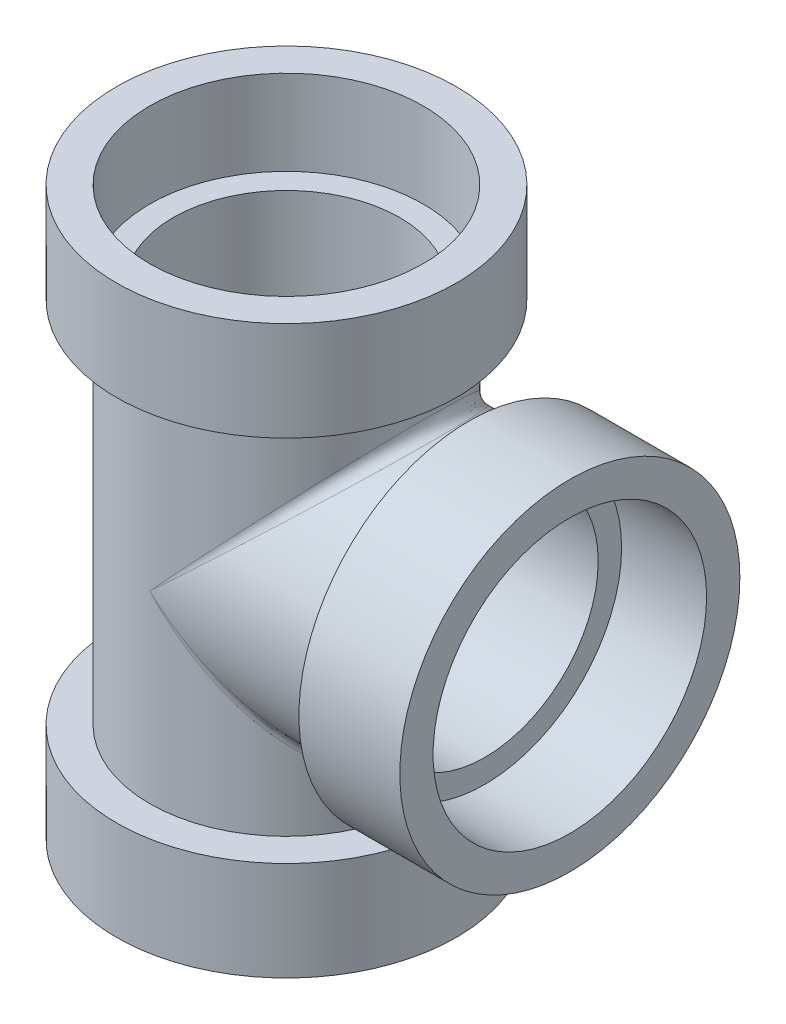
SolidWorks part; units mm, degrees
note: The reader was unsure of these and kept them because the rebuilt part matched: shared geometry of "Croquis3<2>".
ref_plane "Alzado" through (0, 0, 0) normal (0, 0, 1) x (1, 0, 0)
ref_plane "Planta" through (0, 0, 0) normal (0, 1, 0) x (1, 0, 0)
ref_plane "Vista lateral" through (0, 0, 0) normal (1, 0, 0) x (0, 0, -1)
sketch "Croquis1" plane through (0, 0, 0) normal (0, 1, 0) x (1, 0, 0)
  circle A0 centre (0, 0) radius 30
  dimension "D1" = 60
extrude "Saliente-Extruir1" add sketch "Croquis1" along normal mid plane 100
sketch "Croquis3" plane through (0, 50, 0) normal (0, 1, 0) x (1, 0, 0)
  circle A0 centre (0, 0) radius 24.13
  dimension "D1" = 48.26
extrude "Cortar-Extruir1" cut sketch "Croquis3" against normal blind 15
extrude "Cortar-Extruir2" cut sketch "Croquis3<2>" along normal blind 15 from surface at -100 starting at face at (0, -50, 30)
sketch "Croquis3<2>" plane through (0, 50, 0) normal (0, 1, 0) x (1, 0, 0) same geometry as "Croquis3"
sketch "Croquis4" plane through (0, 0, 0) normal (0, 1, 0) x (1, 0, 0)
  circle A0 centre (0, 0) radius 30 construction
  circle A1 centre (0, 0) radius 24.13 construction
  circle A2 centre (0, 0) radius 30
  circle A3 centre (0, 0) radius 24.13
extrude "Cortar-Extruir3" cut sketch "Croquis4" against normal mid plane 65
sketch "Croquis5" plane through (0, 0, 0) normal (1, 0, 0) x (0, 0, -1)
  circle A0 centre (0, 0) radius 24.13
  dimension "D1" = 48.26
extrude "Saliente-Extruir2" add sketch "Croquis5" along normal blind 50
sketch "Croquis6" plane through (50, 0, 0) normal (1, 0, 0) x (0, 0, -1)
  circle A0 centre (0, 0) radius 30
  dimension "D1" = 60
extrude "Saliente-Extruir3" add sketch "Croquis6" against normal blind 17.8
sketch "Croquis7" plane through (50, 0, 0) normal (1, 0, 0) x (0, 0, -1)
  circle A0 centre (0, 0) radius 24.13
  dimension "D1" = 48.26
extrude "Cortar-Extruir4" cut sketch "Croquis7" against normal blind 15
sketch "Croquis9" plane through (0, -35, 0) normal (0, -1, 0) x (1, 0, 0)
  circle A0 centre (0, 0) radius 20
  dimension "D1" = 40
extrude "Cortar-Extruir5" cut sketch "Croquis9" against normal through all
fillet "Redondeo1" radius 2 2 edges at (24.13, -24.13, 0) (24.13, 24.13, 0)
sketch "Croquis10" plane through (35, 0, 0) normal (1, 0, 0) x (0, 0, -1)
  circle A0 centre (0, 0) radius 20
  dimension "D1" = 40
extrude "Cortar-Extruir6" cut sketch "Croquis10" against normal up to surface (35 mm away) up to face at (0, 35, 20)
